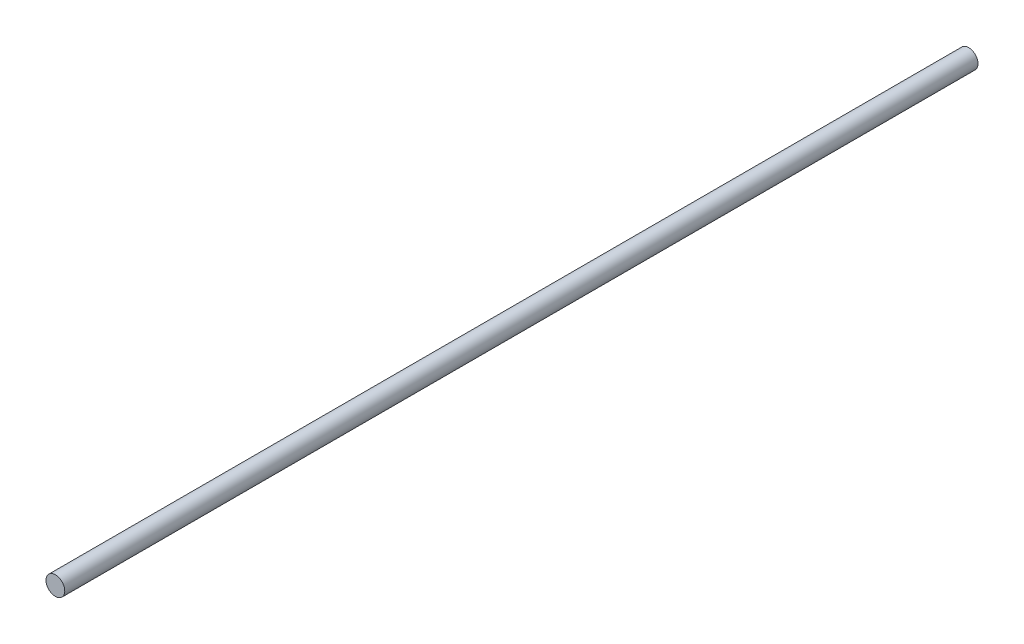
SolidWorks part; units mm, degrees
material "AISI 316 Stainless Steel Sheet (SS)"
ref_plane "Front (1)" through (0, 0, 0) normal (0, 0, 1) x (1, 0, 0)
ref_plane "Top (2)" through (0, 0, 0) normal (0, 1, 0) x (1, 0, 0)
ref_plane "Right (3)" through (0, 0, 0) normal (1, 0, 0) x (0, 0, -1)
ref_axis "X Axis" through (13.5064, 0, 0) along (-1, 0, 0)
ref_axis "Y Axis" through (0, 12.3593, 0) along (0, -1, 0)
ref_axis "Z Axis" through (0, 0, 14.1119) along (0, 0, -1)
sketch "Sketch2" plane through (0, 0, 0) normal (1, 0, 0) x (0, 0, -1)
  line L0 (0, 0) -> (-4, 0) construction
  line L1 (0, 0) -> (389.2, 0)
  line L2 (0, 0) -> (0, 4)
  line L3 (0, 4) -> (389.2, 4)
  line L4 (389.2, 0) -> (389.2, 4)
  dimension "D1" = 8
  dimension "D2" = 389.2
revolve "Revolve1" add sketch "Sketch2" angle 360 about L0
